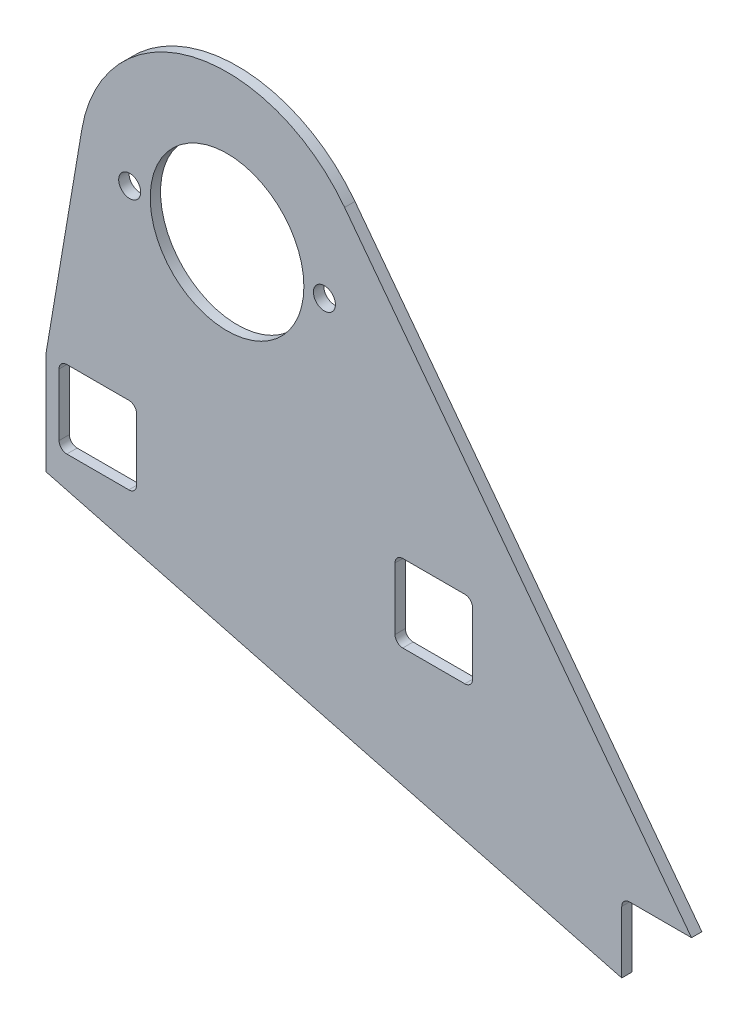
SolidWorks part; units mm, degrees
material "AISI 1020"
ref_plane "Спереди" through (0, 0, 0) normal (0, 0, 1) x (1, 0, 0)
ref_plane "Сверху" through (0, 0, 0) normal (0, 1, 0) x (1, 0, 0)
ref_plane "Справа" through (0, 0, 0) normal (1, 0, 0) x (0, 0, -1)
sketch "Эскиз1" plane through (0, 0, 0) normal (0, 0, 1) x (1, 0, 0)
  line L0 (-33.325, 4.35) -> (-42.025, 4.35) construction
  line L11 (-33.325, -4.35) -> (-33.325, 4.35) construction
  line L12 (-55, 0) -> (55, 0) construction
  line L13 (33.325, 4.35) -> (42.025, 4.35) construction
  line L14 (33.325, -4.35) -> (33.325, 4.35) construction
  line L15 (102, -72) -> (-72, -72) construction
  line L16 (42.025, -4.35) -> (42.025, 4.35) construction
  line L17 (179.7332, -143.2262) -> (45.4927, 34.3841)
  line L18 (-70, -72) -> (-56.2279, 9.5014)
  line L19 (-65, -75) -> (-65, -99) construction
  line L23 (-70, -72) -> (-70, -112)
  line L31 (-70, -112) -> (152.7332, -170.2262)
  line L32 (-62, -102) -> (-38, -102) construction
  line L33 (152.7332, -146.2262) -> (152.7332, -170.2262) construction
  line L34 (179.7332, -143.2262) -> (155.7332, -143.2262) construction
  line L35 (179.7332, -143.2262) -> (155.7332, -143.2262)
  line L36 (152.7332, -146.2262) -> (152.7332, -170.2262)
  line L41 (-62, -102) -> (-38, -102)
  line L42 (-35, -99) -> (-35, -75)
  line L43 (-38, -72) -> (-62, -72)
  line L44 (-65, -75) -> (-65, -99)
  line L45 (-62, -102) -> (-38, -102)
  line L46 (-35, -99) -> (-35, -75)
  line L47 (-38, -72) -> (-62, -72)
  line L48 (-65, -75) -> (-65, -99)
  line L49 (68, -102) -> (92, -102)
  line L50 (95, -99) -> (95, -75)
  line L51 (92, -72) -> (68, -72)
  line L52 (65, -75) -> (65, -99)
  line L53 (68, -102) -> (92, -102)
  line L54 (95, -99) -> (95, -75)
  line L55 (92, -72) -> (68, -72)
  line L56 (65, -75) -> (65, -99)
  line L61 (75.75, -74) -> (84.25, -74) construction
  line L62 (65, -72) -> (95, -72) construction
  line L63 (65, -72) -> (65, -102) construction
  line L64 (65, -102) -> (95, -102) construction
  line L65 (95, -72) -> (95, -102) construction
  circle A0 centre (-37.675, 0) radius 4.25
  circle A1 centre (0, 0) radius 29.7321 construction
  circle A2 centre (0, 0) radius 29.7321
  circle A3 centre (37.675, 0) radius 4.25
  arc A4 (45.4927, 34.3841) -> (-56.2279, 9.5014) centre (0, 0) ccw
  arc A5 (155.7332, -143.2262) -> (152.7332, -146.2262) centre (155.7332, -146.2262) ccw construction
  arc A6 (155.7332, -143.2262) -> (152.7332, -146.2262) centre (155.7332, -146.2262) ccw
  arc A11 (-65, -99) -> (-62, -102) centre (-62, -99) ccw
  arc A12 (-38, -102) -> (-35, -99) centre (-38, -99) ccw
  arc A13 (-35, -75) -> (-38, -72) centre (-38, -75) ccw
  arc A14 (-62, -72) -> (-65, -75) centre (-62, -75) ccw
  arc A15 (-65, -99) -> (-62, -102) centre (-62, -99) ccw
  arc A16 (-38, -102) -> (-35, -99) centre (-38, -99) ccw
  arc A17 (-35, -75) -> (-38, -72) centre (-38, -75) ccw
  arc A18 (-62, -72) -> (-65, -75) centre (-62, -75) ccw
  arc A19 (65, -99) -> (68, -102) centre (68, -99) ccw
  arc A20 (92, -102) -> (95, -99) centre (92, -99) ccw
  arc A21 (95, -75) -> (92, -72) centre (92, -75) ccw
  arc A22 (68, -72) -> (65, -75) centre (68, -75) ccw
  arc A23 (65, -99) -> (68, -102) centre (68, -99) ccw
  arc A24 (92, -102) -> (95, -99) centre (92, -99) ccw
  arc A25 (95, -75) -> (92, -72) centre (92, -75) ccw
  arc A26 (68, -72) -> (65, -75) centre (68, -75) ccw
  point P19 (-37.675, 4.35)
  point P25 (-33.325, 0)
  point P33 (37.675, 4.35)
  point P37 (33.325, 0)
  point P74 (80, -74)
  point P77 (80, -72)
  dimension "D2" = 8.5
  dimension "D3" = 15
  dimension "D1" = 5
  dimension "D4" = 10
  dimension "D5" = 0
  dimension "D7" = 30
  dimension "D6" = 0
base flange "Базовая кромка1" sketch "Эскиз1" thickness 4 reverse thickness direction no parameters "D1"=0.75
sketch "Сгиб-Линии1" [suppressed] plane through (0, 0, 0) normal (0, 1, 0) x (1, 0, 0)
sketch "Граничная рамка1" [suppressed] plane through (0, 0, 0) normal (0, 1, 0) x (1, 0, 0)
sheet metal parameters "Листовой металл3" thickness 4 parameters "D1"=0.75
flat pattern "Развертка3" [suppressed]
sketch "Сгиб-Линии2" plane through (0, 0, 0) normal (0, 1, 0) x (1, 0, 0)
sketch3d "Граничная рамка2" [suppressed]
  line L0 (-196.4816, 215.8198, 0) -> (61.9723, 148.2556, 0) construction
  line L1 (-242.7877, 38.6845, 0) -> (15.6661, -28.8796, 0) construction
  line L2 (-196.4816, 215.8198, 0) -> (-242.7877, 38.6845, 0) construction
  line L3 (61.9723, 148.2556, 0) -> (15.6661, -28.8796, 0) construction
